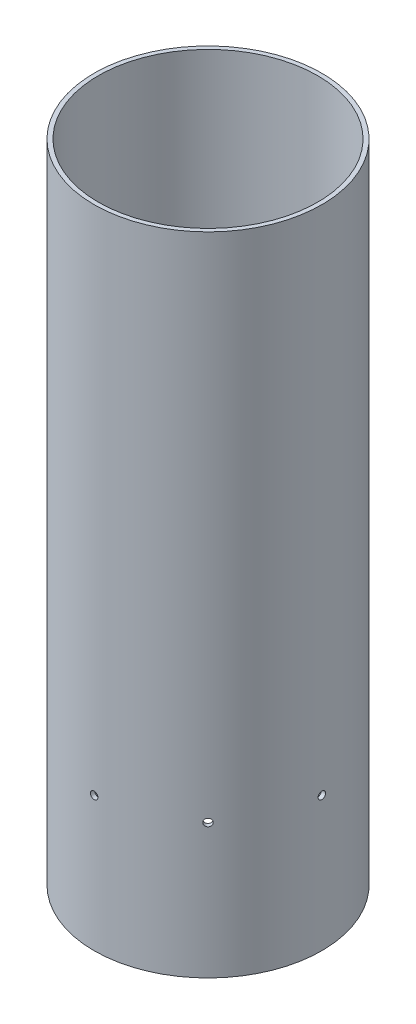
SolidWorks part; units mm, degrees
material "E-Glass Fiber"
ref_plane "Front Plane" through (0, 0, 0) normal (0, 0, 1) x (1, 0, 0)
ref_plane "Top Plane" through (0, 0, 0) normal (0, 1, 0) x (1, 0, 0)
ref_plane "Right Plane" through (0, 0, 0) normal (1, 0, 0) x (0, 0, -1)
sketch "Sketch1" plane through (0, 0, 0) normal (0, 1, 0) x (1, 0, 0)
  circle A0 centre (0, 0) radius 53.721
  circle A1 centre (0, 0) radius 51.7271
  dimension "D1" = 107.442
  dimension "D2" = 103.4542
extrude "Boss-Extrude1" add sketch "Sketch1" along normal blind 304.8
sketch "Sketch2" plane through (0, 0, 0) normal (0, 0, 1) x (1, 0, 0)
  line L2 (0, 0) -> (0, 63.5)
  circle A0 centre (0, 63.5) radius 1.7526
  dimension "D2" = 3.5052
  dimension "D1" = 63.5
extrude "Bulkhead Holes" cut sketch "Sketch2" against normal blind 127 contours A0
pattern_circular "CirPattern1" count 8 over 360 about axis through (0, 304.8, 0) along (0, -1, 0) of "Bulkhead Holes" reverse direction yes
